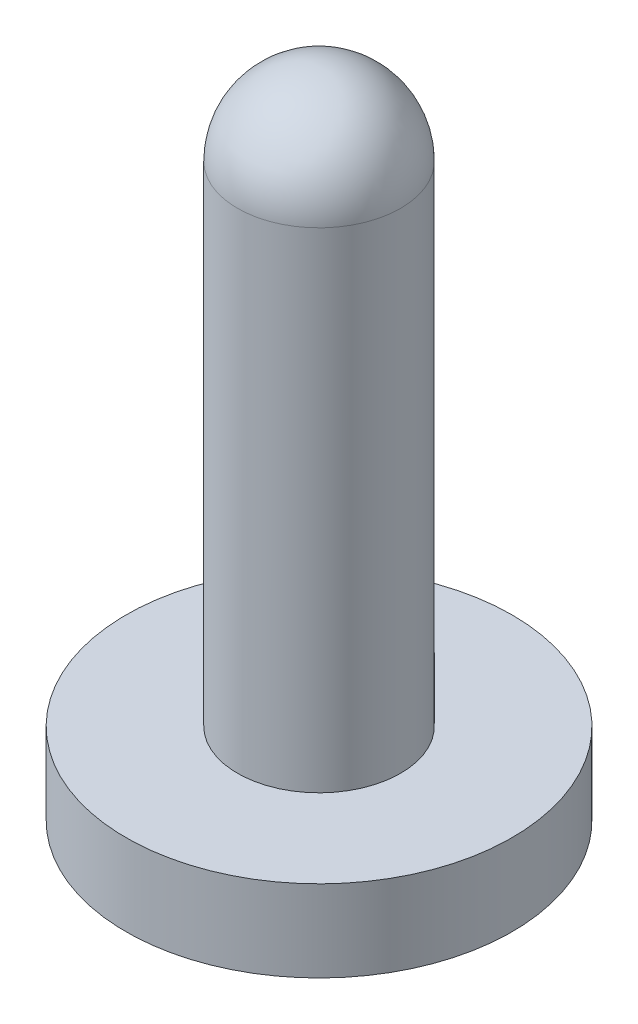
SolidWorks part; units mm, degrees
ref_plane "Front Plane" through (0, 0, 0) normal (0, 0, 1) x (1, 0, 0)
ref_plane "Top Plane" through (0, 0, 0) normal (0, 1, 0) x (1, 0, 0)
ref_plane "Right Plane" through (0, 0, 0) normal (1, 0, 0) x (0, 0, -1)
sketch "Sketch1" plane through (0, 0, 0) normal (0, 1, 0) x (1, 0, 0)
  circle A0 centre (0, 0) radius 1.5
  dimension "D1" = 3
extrude "Boss-Extrude1" add sketch "Sketch1" along normal blind 12
sketch "Sketch6" plane through (0, 0, 0) normal (0, -1, 0) x (1, 0, 0)
  circle A0 centre (0, 0) radius 3.55
  dimension "D1" = 7.1
extrude "Boss-Extrude3" add sketch "Sketch6" against normal blind 1.5
sketch "Sketch2" plane through (0, 0, 0) normal (0, -1, 0) x (1, 0, 0)
  circle A0 centre (0, 0) radius 1
  dimension "D1" = 2
extrude "Cut-Extrude1" cut sketch "Sketch2" against normal blind 10
draft "Draft1" type of draft neutral plane draft angle 1 faces to draft 1 face at (0, 10, -1) neutral plane through (0, 10, 0) neutral plane normal (0, -1, 0) parameters "D1"=1
sketch "Sketch7" plane through (0, 0, 0) normal (0, 0, 1) x (1, 0, 0)
  line L0 (1.5, 1.5) -> (1.5, 12) construction
  line L1 (1.5, 12) -> (-1.5, 12) construction
  line L4 (0, 10.5) -> (0, 12) construction
  line L5 (1.5, 10.5) -> (3.0807, 10.5)
  line L6 (3.0807, 10.5) -> (3.0807, 13.5807)
  line L7 (3.0807, 13.5807) -> (0, 13.5807)
  line L8 (0, 13.5807) -> (0, 12)
  arc A0 (1.5, 10.5) -> (0, 12) centre (0, 10.5) ccw
  point P5 (3.8101, 10.5)
  point P11 (4.5807, 14.2583)
  dimension "D1" = 3.0807
revolve "Cut-Revolve3" cut sketch "Sketch7" angle 360 about L4
sketch "Sketch3" plane through (0, 10, 0) normal (0, -1, 0) x (1, 0, 0)
  line L0 (1.151, 0.2338) -> (0.746, 0)
  line L1 (0.746, 0) -> (1.151, -0.2338)
  line L2 (0, 0) -> (1.1746, 0) construction
  line L3 (1.151, 0.2338) -> (1.151, -0.2338) construction
  line L6 (-0.373, -1.1138) -> (-0.373, -0.6461)
  line L7 (-0.373, -0.6461) -> (-0.778, -0.8799)
  line L10 (-0.373, -1.1138) -> (-0.778, -0.8799) construction
  line L11 (-0.778, 0.8799) -> (-0.373, 0.6461)
  line L14 (-0.373, 0.6461) -> (-0.373, 1.1138)
  line L15 (-0.778, 0.8799) -> (-0.373, 1.1138) construction
  arc A1 (-0.778, -0.8799) -> (-0.373, -1.1138) centre (0, 0) ccw
  arc A2 (-0.373, 1.1138) -> (-0.778, 0.8799) centre (0, 0) ccw
  circle A7 centre (0, 0) radius 1.1746 construction
  arc A8 (1.151, -0.2338) -> (1.151, 0.2338) centre (0, 0) ccw
  circle A9 centre (0, 0) radius 1 construction
  point P16 (0, 0)
  dimension "D1" = 0.254
extrude "Boss-Extrude2" add sketch "Sketch3" along normal up to surface (10 mm away) up to face at (0, 0, 1.1746)
sketch "ref_for_revolve" plane through (0, 0, 0) normal (0, -1, 0) x (1, 0, 0)
  circle A0 centre (0, 0) radius 1.1746 construction
sketch "Sketch4" plane through (0, 0, 0) normal (0, 0, 1) x (1, 0, 0)
  line L1 (1.1746, 0) -> (0.746, 0.4286)
  line L2 (0.746, 0.4286) -> (0, 0.4286)
  line L4 (0, 0.4286) -> (0, 0)
  line L5 (0.746, 0.4286) -> (0.746, 0) construction
  line L6 (0.746, 0) -> (1.1746, 0) construction
  line L7 (1.1746, 0) -> (0, 0)
  line L8 (-0.373, 0) -> (1.151, 0) construction
  line L9 (-1.1746, 0) -> (1.1746, 0) construction
  point P7 (0, 0)
  point P8 (1.2819, 0)
  point P12 (0, 0)
  point P13 (1.368, 0)
  point P14 (1.1559, 0)
  point P17 (0, 0)
revolve "Cut-Revolve1" cut sketch "Sketch4" angle 360 about L4
